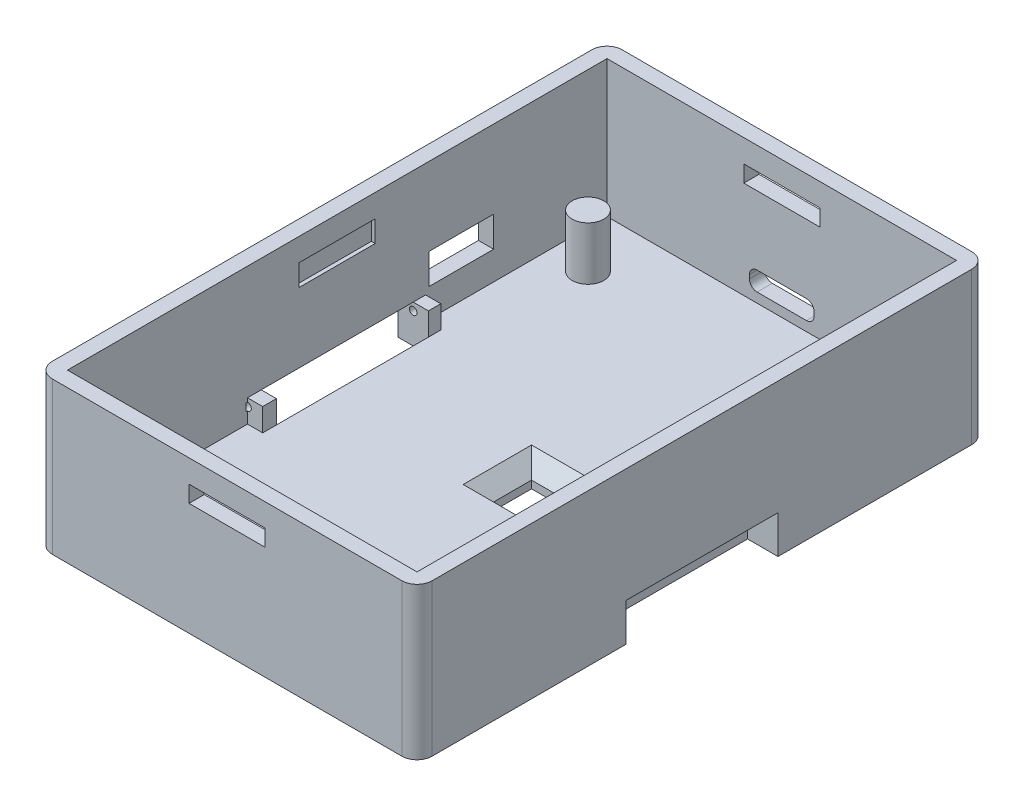
SolidWorks part; units mm, degrees
ref_plane "Front Plane" through (0, 0, 0) normal (0, 0, 1) x (1, 0, 0)
ref_plane "Top Plane" through (0, 0, 0) normal (0, 1, 0) x (1, 0, 0)
ref_plane "Right Plane" through (0, 0, 0) normal (1, 0, 0) x (0, 0, -1)
sketch "Sketch1" plane through (0, 0, 0) normal (0, 1, 0) x (1, 0, 0)
  line L1 (0, 0) -> (50, 0)
  line L2 (0, 0) -> (0, 75)
  line L3 (0, 75) -> (50, 75)
  line L4 (50, 0) -> (50, 75)
  dimension "D1" = 50
  dimension "D2" = 75
extrude "Boss-Extrude1" add sketch "Sketch1" along normal blind 20
shell "Shell1" thickness 2 removed face at (25, 20, -37.5)
fillet "Fillet1" radius 2 4 edges at (0, 10, 0) (0, 10, -75) (50, 10, 0) (50, 10, -75)
sketch "Sketch2" plane through (0, 0, 0) normal (0, -1, 0) x (1, 0, 0)
  circle A0 centre (25, -37.5) radius 12.5
  dimension "D1" = 25
extrude "Boss-Extrude2" add sketch "Sketch2" along normal blind 1
fillet "Fillet2" radius 2 1 edges at (25, -1, -50)
sketch "Sketch3" plane through (0, -1, 0) normal (0, -1, 0) x (1, 0, 0)
  line L0 (33.0724, -37.5) -> (33, -37.5)
  line L1 (33, -39.9586) -> (33.0724, -40) construction
  line L5 (33, -40) -> (33, -35)
  line L6 (33, -37.5) -> (33.0724, -37.5)
  line L8 (25.0724, -40) -> (33.0724, -40)
  line L9 (25.0724, -40) -> (25.0724, -35)
  line L10 (25.0724, -35) -> (33.0724, -35)
  line L11 (33.0724, -40) -> (33.0724, -35)
  line L12 (25, -37.5) -> (25.0724, -37.5)
  line L14 (25.0724, -37.5) -> (25, -37.5)
  line L15 (33, -36.0414) -> (33.0724, -35) construction
  point P5 (25.0724, -37.5)
  point P10 (28.5724, -37.5)
  dimension "D3" = 8
  dimension "D4" = 5
extrude "Cut-Extrude1" cut sketch "Sketch3" against normal blind 5 contours L10 L9 L8 L5 region at (29.0362, -1, -37.5)
sketch "Sketch4" plane through (0, 2, 0) normal (0, 1, 0) x (1, 0, 0)
  line L2 (0, 73) -> (0, 2) construction
  line L5 (48, 75) -> (2, 75) construction
  circle A0 centre (7, 65.5) radius 2.0847
  circle A1 centre (43, 65.5) radius 2.5441
  circle A2 centre (43, 9.5) radius 2.8619
  circle A3 centre (7, 9.5) radius 2.4149
  dimension "D1" = 36
  dimension "D2" = 7
  dimension "D3" = 56
  dimension "D4" = 9.5
extrude "Boss-Extrude3" add sketch "Sketch4" along normal blind 7
chamfer "Chamfer1" distance 2 angle 45 4 edges at (33, 2, -37.5) (29.0362, 2, -40) (25.0724, 2, -37.5) (29.0362, 2, -35)
sketch "Sketch5" plane through (0, 0, 0) normal (-1, 0, 0) x (0, 0, 1)
  line L1 (-73, 0) -> (-2, 0) construction
  line L2 (-37.5, 0) -> (-27.5, 0)
  line L3 (-37.5, 0) -> (-47.5, 0)
  line L4 (-50, 0) -> (-25, 0) construction
  line L5 (-27.5, 0) -> (-27.5, 5)
  line L6 (-27.5, 5) -> (-47.5, 5)
  line L7 (-47.5, 5) -> (-47.5, 0)
  dimension "D1" = 10
  dimension "D2" = 10
  dimension "D3" = 5
extrude "Cut-Extrude2" cut sketch "Sketch5" against normal blind 4
sketch "Sketch7" plane through (0, 2, 0) normal (0, 1, 0) x (1, 0, 0)
  line L1 (2, 47.5) -> (4, 47.5)
  line L2 (2, 47.5) -> (2, 49.1276)
  line L3 (2, 49.1276) -> (4, 49.1276)
  line L4 (4, 47.5) -> (4, 49.1276)
extrude "Boss-Extrude4" add sketch "Sketch7" along normal blind 3
sketch "Sketch8" plane through (0, 2, 0) normal (0, 1, 0) x (1, 0, 0)
  line L1 (2, 27.5) -> (4, 27.5)
  line L2 (2, 27.5) -> (2, 25.6911)
  line L3 (2, 25.6911) -> (4, 25.6911)
  line L4 (4, 27.5) -> (4, 25.6911)
extrude "Boss-Extrude5" add sketch "Sketch8" along normal blind 3
sketch "Sketch9" plane through (0, 0, -47.5) normal (0, 0, 1) x (1, 0, 0)
  line L1 (2, 5) -> (0, 5) construction
  circle A0 centre (2, 4) radius 0.5
  dimension "D2" = 1
  dimension "D1" = 1
extrude "Cut-Extrude3" cut sketch "Sketch9" against normal blind 2
sketch "Sketch10" plane through (0, 0, -27.5) normal (0, 0, -1) x (-1, 0, 0)
  line L0 (-4, 5) -> (-2, 5) construction
  line L1 (-2, 5) -> (-2, 3.2022)
  circle A0 centre (-2, 4) radius 0.5
  dimension "D1" = 1
  dimension "D2" = 1
extrude "Cut-Extrude4" cut sketch "Sketch10" against normal blind 2 contours L1 A0 | L1 A0 region at (1.7878, 4, -27.5) region at (2.2122, 4, -27.5)
ref_plane "Plane1" through (25, 0, 0) normal (1, 0, 0) x (0, 0, -1)
mirror "Mirror1" about plane through (25, 0, 0) normal (1, 0, 0) of "Cut-Extrude2", "Boss-Extrude4", "Boss-Extrude5", "Cut-Extrude3", "Cut-Extrude4"
sketch "Sketch12" plane through (0, 0, 0) normal (-1, 0, 0) x (0, 0, 1)
  line L1 (-58.0841, 9.7354) -> (-49.5841, 9.7354)
  line L2 (-58.0841, 9.7354) -> (-58.0841, 5.7354)
  line L3 (-58.0841, 5.7354) -> (-49.5841, 5.7354)
  line L4 (-49.5841, 9.7354) -> (-49.5841, 5.7354)
  dimension "D1" = 4
  dimension "D2" = 8.5
extrude "Cut-Extrude5" cut sketch "Sketch12" against normal blind 3
sketch "Sketch14" plane through (0, 0, -2) normal (0, 0, -1) x (-1, 0, 0)
  line L1 (-30, 17) -> (-20, 17)
  line L2 (-30, 17) -> (-30, 14.811)
  line L3 (-30, 14.811) -> (-20, 14.811)
  line L4 (-20, 17) -> (-20, 14.811)
  line L6 (-25, 11.55) -> (-25, -11.55) construction
  line L7 (-2, 20) -> (-48, 20) construction
  point P4 (-25, 17)
  dimension "D1" = 10
  dimension "D2" = 3
extrude "Cut-Extrude7" cut sketch "Sketch14" against normal blind 3
ref_plane "Plane2" through (0, 0, -37.5) normal (0, 0, 1) x (1, 0, 0)
sketch "Sketch15" plane through (2, 0, 0) normal (1, 0, 0) x (0, 0, -1)
  line L1 (32.5, 17) -> (42.5, 17)
  line L2 (32.5, 17) -> (32.5, 14.175)
  line L3 (32.5, 14.175) -> (42.5, 14.175)
  line L4 (42.5, 17) -> (42.5, 14.175)
  line L6 (37.5, 11.55) -> (37.5, -11.55) construction
  line L7 (73, 20) -> (2, 20) construction
  point P4 (37.5, 14.175)
  dimension "D1" = 10
  dimension "D2" = 3
extrude "Cut-Extrude8" cut sketch "Sketch15" against normal blind 0.5
mirror "Mirror2" about plane through (0, 0, -37.5) normal (0, 0, 1) of "Cut-Extrude7"
mirror "Mirror3" about plane through (25, 0, 0) normal (1, 0, 0) of "Cut-Extrude8"
sketch "Sketch16" plane through (0, 0, -75) normal (0, 0, -1) x (-1, 0, 0)
  line L0 (-28.25, 5.7698) -> (-21.75, 5.7698)
  line L1 (-29.25, 4.7698) -> (-29.25, 4.2698)
  line L2 (-28.25, 3.2698) -> (-21.75, 3.2698)
  line L3 (-20.75, 4.7698) -> (-20.75, 4.2698)
  arc A0 (-21.75, 5.7698) -> (-20.75, 4.7698) centre (-21.75, 4.7698) cw
  arc A1 (-21.75, 3.2698) -> (-20.75, 4.2698) centre (-21.75, 4.2698) ccw
  arc A2 (-29.25, 4.2698) -> (-28.25, 3.2698) centre (-28.25, 4.2698) ccw
  arc A3 (-28.25, 5.7698) -> (-29.25, 4.7698) centre (-28.25, 4.7698) ccw
  dimension "D1" = 1
extrude "Cut-Extrude9" cut sketch "Sketch16" against normal blind 3
